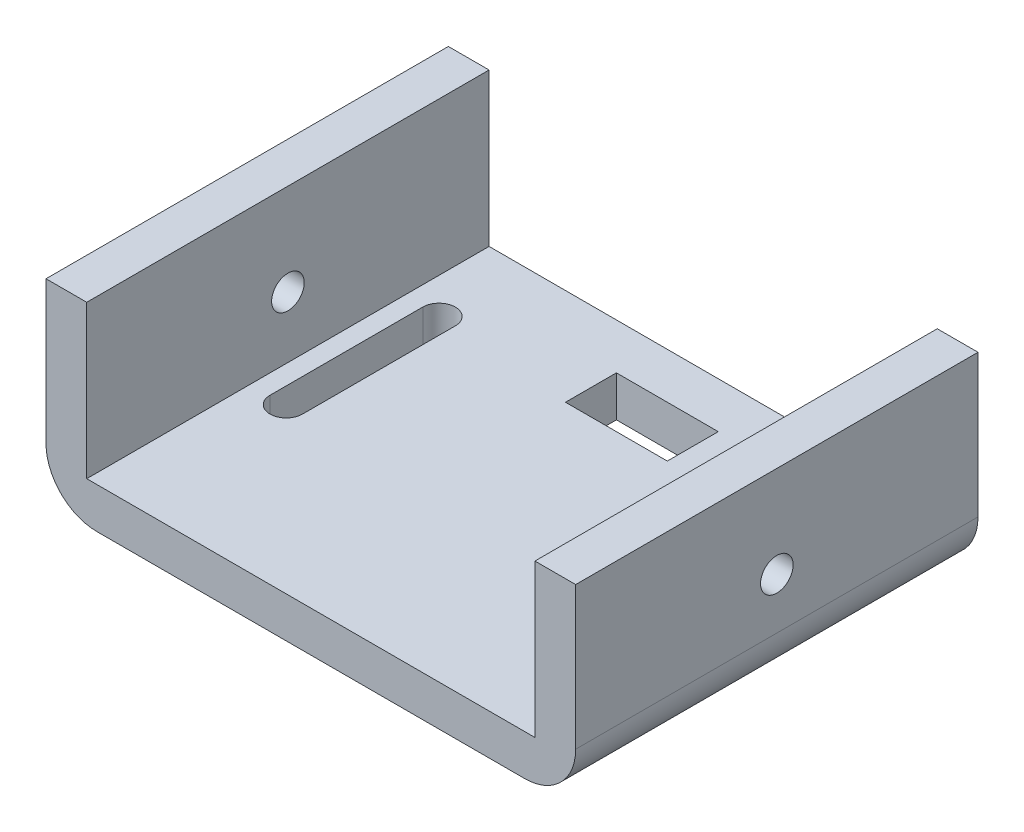
SolidWorks part; units mm, degrees
ref_plane "Plan de face" through (0, 0, 0) normal (0, 0, 1) x (1, 0, 0)
ref_plane "Plan de dessus" through (0, 0, 0) normal (0, 1, 0) x (1, 0, 0)
ref_plane "Plan de droite" through (0, 0, 0) normal (1, 0, 0) x (0, 0, -1)
sketch "Esquisse1" plane through (0, 0, 0) normal (0, 0, 1) x (1, 0, 0)
  line L0 (-22, 0) -> (22, 0)
  line L5 (22, 0) -> (22, 15)
  line L6 (0, 21.1762) -> (0, 6.9257) construction
  line L7 (-22, 0) -> (-22, 15)
  line L8 (-22, 15) -> (-26, 15)
  line L9 (-26, 15) -> (-26, -4)
  line L10 (-26, -4) -> (26, -4)
  line L11 (26, -4) -> (26, 15)
  line L12 (26, 15) -> (22, 15)
  point P8 (0, 0)
  dimension "D1" = 22
  dimension "D2" = 15
  dimension "D3" = 4
  dimension "D4" = 4
  dimension "D5" = 4
  dimension "D6" = 4
extrude "Boss.-Extru.1" add sketch "Esquisse1" along normal blind 39.5
ref_plane "Plan1" through (179.5, -192, -20) normal (-1, 0, 0) x (0, 0, 1)
sketch "Esquisse3" plane through (0, -4, 0) normal (0, -1, 0) x (1, 0, 0)
  line L1 (5, 4.5) -> (-5, 4.5)
  line L2 (5, 4.5) -> (5, 9.5)
  line L3 (5, 9.5) -> (-5, 9.5)
  line L4 (-5, 4.5) -> (-5, 9.5)
  line L5 (5, 4.5) -> (-5, 9.5) construction
  line L6 (5, 9.5) -> (-5, 4.5) construction
  line L7 (-26, 39.5) -> (26, 39.5) construction
  line L8 (-26, 0) -> (26, 0) construction
  point P4 (0, 0)
  point P6 (0, 7)
  dimension "D1" = 10
  dimension "D2" = 5
  dimension "D4" = 30
extrude "Enlèv. mat.-Extru.1" cut sketch "Esquisse3" against normal through all
sketch "Sketch1" plane through (-22, 0, 0) normal (1, 0, 0) x (0, 0, -1)
  circle A0 centre (-19.75, 6) radius 1.6
extrude "Cut-Extrude1" cut sketch "Sketch1" against normal through all and the other way through all
sketch "Sketch2" plane through (0, -4, 0) normal (0, -1, 0) x (1, 0, 0)
  line L0 (-18.5, 23.4112) -> (-18.5, 8.4112) construction
  line L1 (-16.9, 23.4112) -> (-16.9, 8.4112)
  line L2 (-20.1, 23.4112) -> (-20.1, 8.4112)
  line L3 (18.5, 23.4112) -> (18.5, 8.4112) construction
  line L4 (20.1, 23.4112) -> (20.1, 8.4112)
  line L5 (16.9, 23.4112) -> (16.9, 8.4112)
  arc A1 (-16.9, 23.4112) -> (-20.1, 23.4112) centre (-18.5, 23.4112) ccw
  arc A2 (-20.1, 8.4112) -> (-16.9, 8.4112) centre (-18.5, 8.4112) ccw
  arc A3 (20.1, 23.4112) -> (16.9, 23.4112) centre (18.5, 23.4112) ccw
  arc A4 (16.9, 8.4112) -> (20.1, 8.4112) centre (18.5, 8.4112) ccw
  point P3 (-18.5, 15.9112)
  point P12 (18.5, 15.9112)
  dimension "D1" = 1.6
  dimension "D2" = 15
extrude "Cut-Extrude2" cut sketch "Sketch2" against normal through all
fillet "Fillet1" radius 5 2 edges at (26, -4, 19.75) (-26, -4, 19.75)
